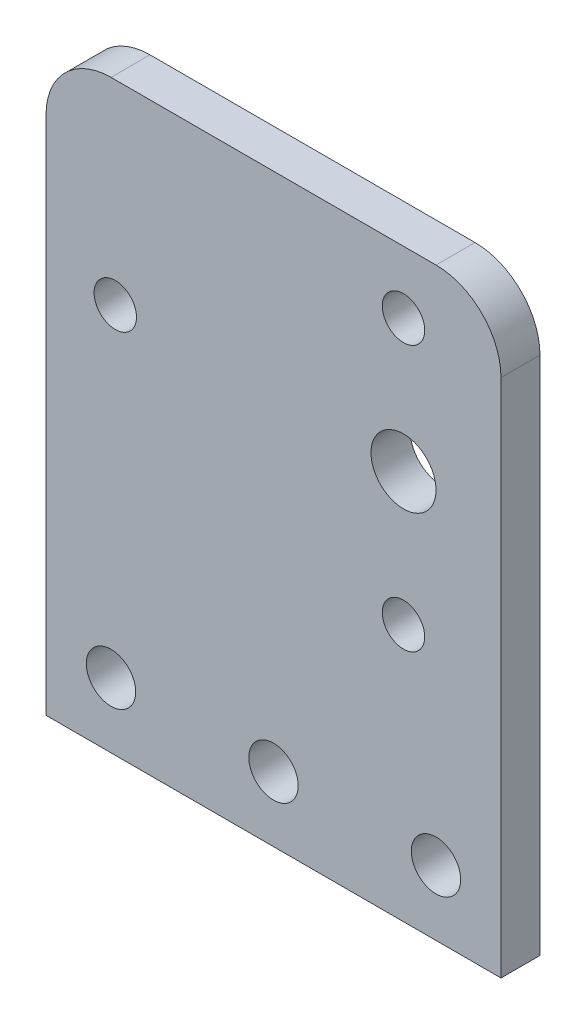
SolidWorks part; units mm, degrees
ref_plane "Front Plane" through (0, 0, 0) normal (0, 0, 1) x (1, 0, 0)
ref_plane "Top Plane" through (0, 0, 0) normal (0, 1, 0) x (1, 0, 0)
ref_plane "Right Plane" through (0, 0, 0) normal (1, 0, 0) x (0, 0, -1)
sketch "Sketch1" plane through (0, 0, 0) normal (0, 0, 1) x (1, 0, 0)
  line L1 (-17.5, 22.5) -> (17.5, 22.5)
  line L2 (-17.5, 22.5) -> (-17.5, -22.5)
  line L3 (-17.5, -22.5) -> (17.5, -22.5)
  line L4 (17.5, 22.5) -> (17.5, -22.5)
  line L5 (-17.5, 22.5) -> (17.5, -22.5) construction
  line L6 (-17.5, -22.5) -> (17.5, 22.5) construction
  circle A0 centre (10, 7.5) radius 2.5
  point P0 (0, 0)
  dimension "D3" = 5
  dimension "D1" = 35
  dimension "D2" = 45
  dimension "D4" = 27.5
  dimension "D5" = 30
extrude "Boss-Extrude1" add sketch "Sketch1" along normal blind 3
hole_wizard "#4 Clearance Hole1" positions "Sketch2" profile "Sketch3" hole size "#4" standard "ANSI Inch" end condition up to next
sketch "Sketch2" plane through (0, 0, 3) normal (0, 0, 1) x (1, 0, 0)
  circle A1 centre (10, 7.5) radius 2.5 construction
  circle A2 centre (1.28, 7.5) radius 17.57 construction
  point P0 (10, 17.71)
  point P2 (10, -2.71)
  point P4 (-12.17, 7.5)
  dimension "D1" = 35.14
  dimension "D4" = 10.21
  dimension "D5" = 10.21
  dimension "D6" = 22.17
  dimension "D7" = 10.21
  dimension "D2" = 8.72
  dimension "D3" = 8.72
sketch "Sketch3" plane through (10, 17.71, 3) normal (1, 0, 0) x (0, -1, 0)
  line L0 (0, 0) -> (0, 3)
  line L1 (0, 3) -> (1.6319, 3)
  line L2 (1.6319, 3) -> (1.6319, 0)
  line L5 (1.6319, 0) -> (0, 0)
  line L11 (0, -6.35) -> (0, 107.95) construction
  dimension "Thru Hole Dia." = 3.2639
  dimension "Thru Hole Depth" = 3
fillet "Fillet1" radius 5 2 edges at (17.5, 22.5, 1.5) (-17.5, 22.5, 1.5)
hole_wizard "#6 Clearance Hole1" positions "Sketch4" profile "Sketch5" hole size "#6" standard "ANSI Inch" end condition up to next
sketch "Sketch4" plane through (0, 0, 3) normal (0, 0, 1) x (1, 0, 0)
  line L0 (-17.5, -22.5) -> (17.5, -22.5) construction
  line L1 (-17.5, 17.5) -> (-17.5, -22.5) construction
  line L2 (17.5, -22.5) -> (17.5, 17.5) construction
  point P0 (-12.5, -17.5)
  point P2 (0, -17.5)
  point P4 (12.5, -17.5)
  dimension "D1" = 5
  dimension "D2" = 5
  dimension "D3" = 5
sketch "Sketch5" plane through (-12.5, -17.5, 3) normal (1, 0, 0) x (0, -1, 0)
  line L0 (0, 0) -> (0, 3)
  line L1 (0, 3) -> (1.8986, 3)
  line L2 (1.8986, 3) -> (1.8986, 0)
  line L5 (1.8986, 0) -> (0, 0)
  line L11 (0, -6.35) -> (0, 107.95) construction
  dimension "Thru Hole Dia." = 3.7973
  dimension "Thru Hole Depth" = 3
equation "\"D3@Sketch4\"=\"D2@Sketch4\""
equation "\"D5@Sketch2\"=\"D4@Sketch2\""
equation "\"D4@Sketch1\"=\"D1@Sketch1\"-7.5"
equation "\"D7@Sketch2\"=\"D4@Sketch2\""
